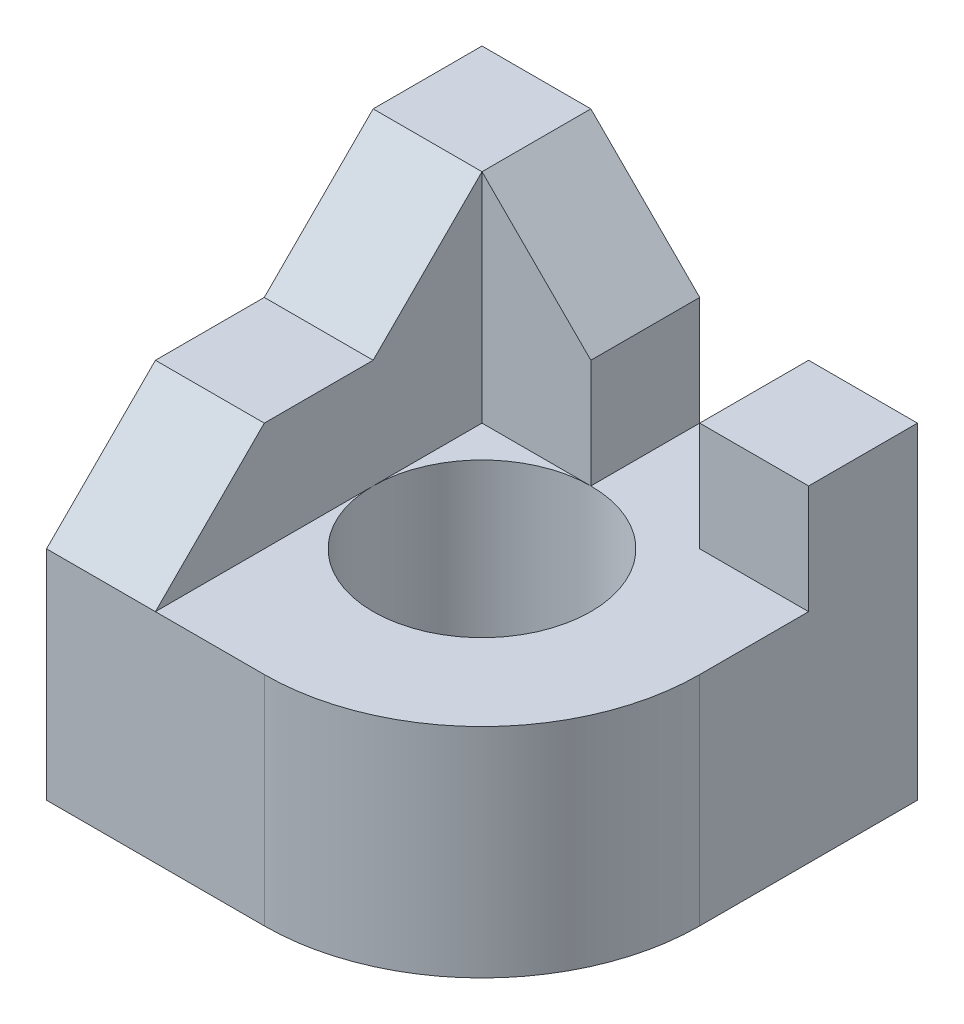
SolidWorks part; units mm, degrees
note: The reader was unsure of these and kept them because the rebuilt part matched: shared geometry of "Sketch1<3>", "Sketch1<4>".
ref_plane "Front Plane" through (0, 0, 0) normal (0, 0, 1) x (1, 0, 0)
ref_plane "Top Plane" through (0, 0, 0) normal (0, 1, 0) x (1, 0, 0)
ref_plane "Right Plane" through (0, 0, 0) normal (1, 0, 0) x (0, 0, -1)
sketch "Sketch1" plane through (0, 0, 0) normal (0, 1, 0) x (1, 0, 0)
  line L0 (0, 0) -> (0, -40)
  line L1 (0, -40) -> (20, -40)
  line L2 (40, -20) -> (40, 0)
  line L3 (40, 0) -> (0, 0)
  line L4 (10, 0) -> (10, -40)
  line L5 (10, -10) -> (20, -10)
  line L6 (30, -10) -> (30, 0)
  line L7 (20, -10) -> (20, 0)
  line L8 (30, -10) -> (40, -10)
  arc A0 (20, -40) -> (40, -20) centre (20, -20) ccw
  circle A1 centre (20, -20) radius 10
  dimension "D3" = 20
  dimension "D5" = 20
  dimension "D1" = 40
  dimension "D2" = 40
  dimension "D4" = 20
  dimension "D6" = 10
  dimension "D7" = 10
  dimension "D8" = 10
extrude "Boss-Extrude1" add sketch "Sketch1" along normal blind 20 contours L4 L3 L0 L1 | A1 L4 L1 A0 L2 L8 L6 L3 L7 | L5 L7 L3 L4 | L6 L8 L2 L3 | A1 L5 L4
extrude "Boss-Extrude2" add sketch "Sketch1<3>" along normal blind 30 contours L6 L8 L2 L3
sketch "Sketch1<3>" plane through (0, 0, 0) normal (0, 1, 0) x (1, 0, 0) same geometry as "Sketch1"
extrude "Boss-Extrude3" add sketch "Sketch1<4>" along normal blind 40 contours L5 L7 L3 L4 | L4 L3 L0 L1
sketch "Sketch1<4>" plane through (0, 0, 0) normal (0, 1, 0) x (1, 0, 0) same geometry as "Sketch1"
sketch "Sketch2" plane through (0, 0, 10) normal (0, 0, 1) x (1, 0, 0)
  line L0 (10, 40) -> (20, 30)
  line L1 (20, 40) -> (20, 20) construction
extrude "Cut-Extrude1" cut sketch "Sketch2" against normal blind 10 and the other way through all contours L0
sketch "Sketch3" plane through (10, 0, 0) normal (1, 0, 0) x (0, 0, -1)
  line L0 (-40, 20) -> (-30, 30)
  line L1 (-30, 30) -> (-20, 30)
  line L2 (-20, 30) -> (-10, 40)
  line L3 (-40, 20) -> (-20, 20) construction
  point P8 (-30, 20)
  dimension "D1" = 10
  dimension "D2" = 10
  dimension "D3" = 10
extrude "Cut-Extrude2" cut sketch "Sketch3" against normal blind 10 and the other way through all
